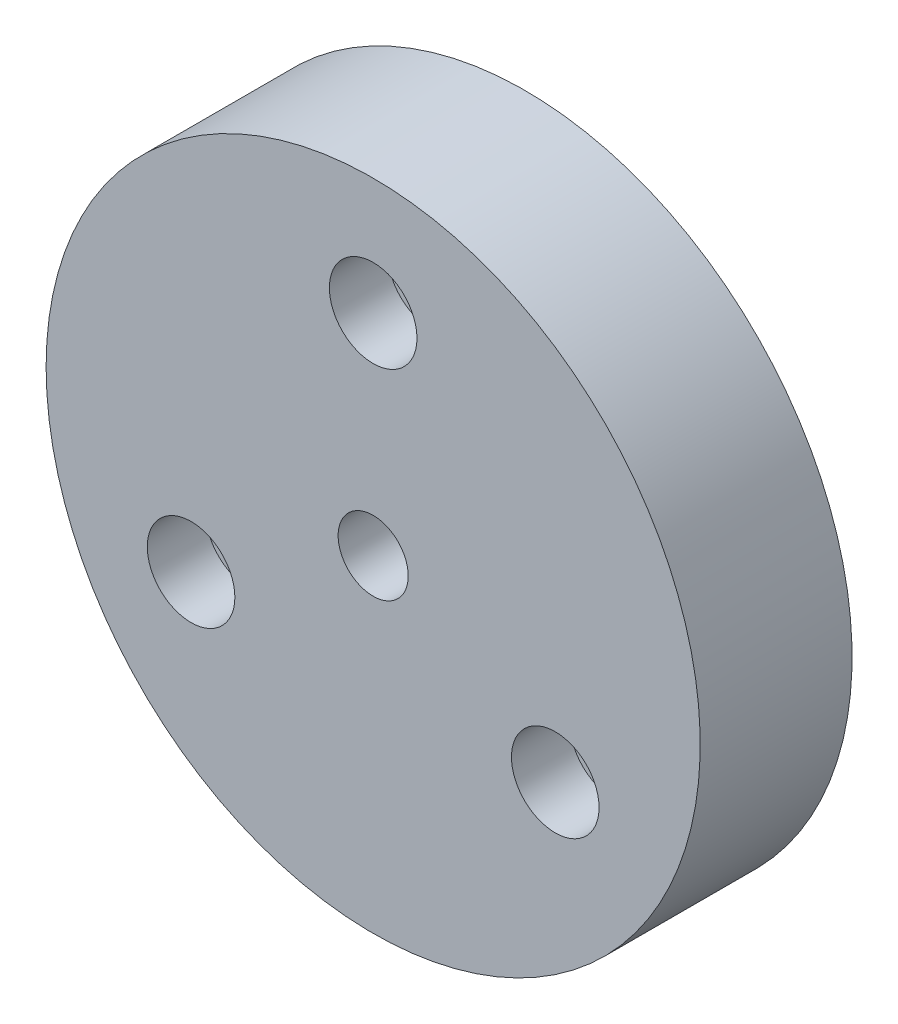
SolidWorks part; units mm, degrees
ref_plane "Front" through (0, 0, 0) normal (0, 0, 1) x (1, 0, 0)
ref_plane "Top" through (0, 0, 0) normal (0, 1, 0) x (1, 0, 0)
ref_plane "Right" through (0, 0, 0) normal (1, 0, 0) x (0, 0, -1)
sketch "Esquisse1" plane through (0, 0, 0) normal (0, 0, 1) x (1, 0, 0)
  circle A0 centre (0, 0) radius 28
  dimension "D1" = 56
extrude "Boss.-Extru.1" add sketch "Esquisse1" along normal blind 13
sketch "Esquisse2" plane through (0, 0, 13) normal (0, 0, 1) x (1, 0, 0)
  circle A0 centre (0, 0) radius 3
  dimension "D1" = 6
extrude "Enlèv. mat.-Extru.1" cut sketch "Esquisse2" against normal through all
sketch "Esquisse3" plane through (0, 0, 13) normal (0, 0, 1) x (1, 0, 0)
  line L1 (0, 0) -> (0, 18) construction
  circle A0 centre (0, 18) radius 1.65
  circle A1 centre (15.5885, -9) radius 1.65
  circle A2 centre (-15.5885, -9) radius 1.65
  point P5 (20.8744, -9.1794)
  point P6 (0, 0)
  point P10 (0, 0)
  dimension "D1" = 3.3
  dimension "D2" = 18
  dimension "D3" = 3
extrude "Enlèv. mat.-Extru.2" cut sketch "Esquisse3" against normal through all
sketch "Esquisse4" plane through (0, 0, 13) normal (0, 0, 1) x (1, 0, 0)
  circle A0 centre (0, 18) radius 3.75
  circle A1 centre (15.5885, -9) radius 3.75
  circle A2 centre (-15.5885, -9) radius 3.75
  dimension "D1" = 7.5
extrude "Enlèv. mat.-Extru.3" cut sketch "Esquisse4" against normal blind 5
